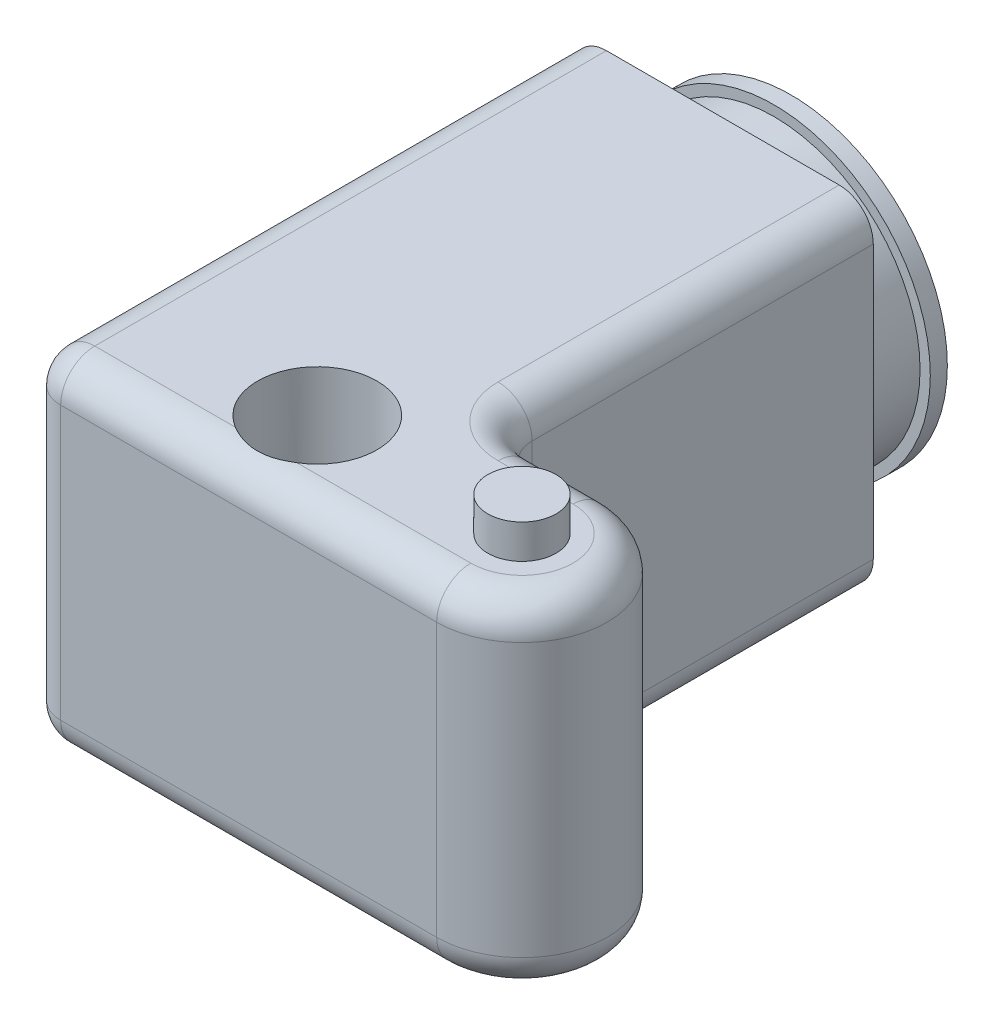
SolidWorks part; units mm, degrees
ref_plane "Front Plane" through (0, 0, 0) normal (0, 0, 1) x (1, 0, 0)
ref_plane "Top Plane" through (0, 0, 0) normal (0, 1, 0) x (1, 0, 0)
ref_plane "Right Plane" through (0, 0, 0) normal (1, 0, 0) x (0, 0, -1)
sketch "Sketch1" plane through (0, 0, 0) normal (0, 1, 0) x (1, 0, 0)
  line L3 (38.2193, 35.3917) -> (95.2257, 35.3917)
  line L4 (95.2257, 35.3917) -> (95.2257, -14.6083)
  line L5 (95.2257, -14.6083) -> (-50, -14.6083)
  line L9 (-50, -14.6083) -> (-50, 145.3917)
  line L10 (-50, 145.3917) -> (38.2193, 145.3917)
  line L11 (38.2193, 145.3917) -> (38.2193, 35.3917)
  line L12 (38.2193, 35.3917) -> (-50, 35.3917) construction
  dimension "D1" = 110
  dimension "D2" = 50
  dimension "D3" = 90
extrude "Boss-Extrude1" add sketch "Sketch1" along normal mid plane 100
sketch "Sketch3" plane through (0, 50, 0) normal (0, 1, 0) x (1, 0, 0)
  line L0 (95.2257, 10.3917) -> (70.2257, 10.3917) construction
  line L1 (95.2257, -14.6083) -> (95.2257, 35.3917) construction
  line L2 (70.2257, 10.3917) -> (70.2257, -14.6083) construction
  line L3 (-50, -14.6083) -> (95.2257, -14.6083) construction
  circle A0 centre (70.2257, 10.3917) radius 10
  dimension "D1" = 20
extrude "Boss-Extrude2" add sketch "Sketch3" along normal blind 10
sketch "Sketch4" plane through (0, 0, -145.3917) normal (0, 0, -1) x (-1, 0, 0)
  line L0 (-38.2193, 50) -> (50, 50) construction
  line L1 (5.8904, 50) -> (5.8904, 0) construction
  line L2 (5.8904, 0) -> (50, 0) construction
  line L3 (50, 50) -> (50, -50) construction
  circle A0 centre (5.8904, 0) radius 42.8283
  dimension "D1" = 85.6567
extrude "Boss-Extrude3" add sketch "Sketch4" along normal blind 15
sketch "Sketch5" plane through (0, 0, -160.3917) normal (0, 0, -1) x (-1, 0, 0)
  circle A2 centre (5.8904, 0) radius 45.8283
  circle A3 centre (5.8904, 0) radius 45.8283
  dimension "D1" = 3
extrude "Boss-Extrude4" add sketch "Sketch5" along normal blind 5
fillet "Fillet1" 2 edges at (95.2257, 0, -35.3917) (95.2257, 0, 14.6083) type full round first side face at (66.7225, 0, -35.3917) second side face at (22.6128, 0, 14.6083) middle face at (95.2257, 0, -10.3917)
sketch "Sketch6" plane through (0, 50, 0) normal (0, 1, 0) x (1, 0, 0)
  line L0 (10.2257, 10.3917) -> (70.2257, 10.3917) construction
  circle A0 centre (10.2257, 10.3917) radius 17.5
  circle A1 centre (70.2257, 10.3917) radius 10 construction
  dimension "D1" = 35
  dimension "D2" = 60
extrude "Cut-Extrude1" cut sketch "Sketch6" against normal blind 25
mirror "Mirror1" about plane through (0, 0, 0) normal (0, 1, 0) of "Cut-Extrude1"
fillet "Fillet2" radius 10 12 edges at (38.2193, -50, -90.3917) (38.2193, 50, -90.3917) (54.2225, -50, -35.3917) (95.2257, -50, -10.3917) (54.2225, 50, -35.3917) (95.2257, 50, -10.3917) (-50, -50, -65.3917) (10.1128, -50, 14.6083) (10.1128, 50, 14.6083) (-50, 50, -65.3917) (-50, 0, 14.6083) (38.2193, 0, -35.3917)
